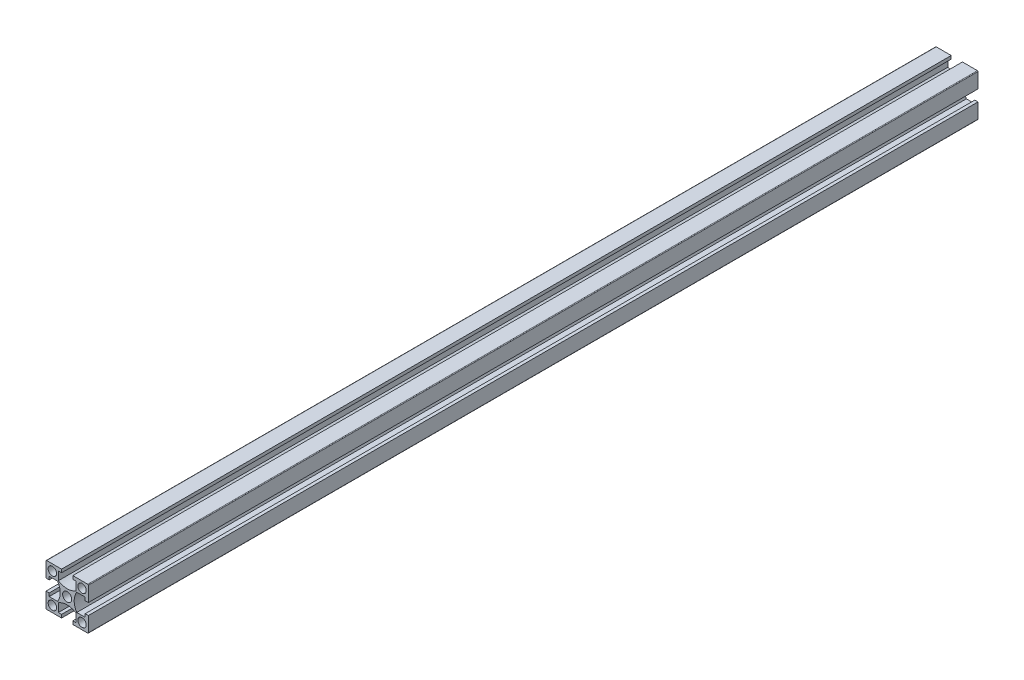
SolidWorks part; units mm, degrees
material "3.0255 (EN-AW 1350A)"
ref_plane "정면" through (0, 0, 0) normal (0, 0, 1) x (1, 0, 0)
ref_plane "윗면" through (0, 0, 0) normal (0, 1, 0) x (1, 0, 0)
ref_plane "우측면" through (0, 0, 0) normal (1, 0, 0) x (0, 0, -1)
sketch "스케치1" plane through (0, 0, 0) normal (0, 0, 1) x (1, 0, 0)
  line L0 (0, 32.0265) -> (0, -31.6588) construction
  line L1 (-10, 10) -> (-10, -10)
  line L2 (-10, 10) -> (10, 10)
  line L3 (-10, 2.65) -> (-8.5, 2.65)
  line L4 (13.6618, 0) -> (-11.6993, 0) construction
  line L5 (-8.5, 2.65) -> (-8.5, 4.15)
  line L6 (-8.5, 4.15) -> (-4.5032, 4.15)
  line L7 (-10, -2.65) -> (-8.5, -2.65)
  line L8 (-8.5, -2.65) -> (-8.5, -4.15)
  line L9 (-8.5, -4.15) -> (-4.5032, -4.15)
  line L10 (-10, -10) -> (10, -10)
  line L11 (10, 10) -> (10, -10)
  circle A0 centre (-7, 7) radius 2
  circle A1 centre (-7, -7) radius 2
  arc A2 (-4.5032, 4.15) -> (-4.5032, -4.15) centre (-11.0587, 0) cw
  circle A3 centre (0, 0) radius 2.15
  circle A4 centre (7, 7) radius 2
  circle A5 centre (7, -7) radius 2
  point P21 (-10, 0)
  point P23 (-3.3, 0)
  point P31 (0, -10)
  point P32 (0, 10)
  dimension "D3" = 4
  dimension "D9" = 6.7
  dimension "D10" = 4.3
  dimension "D11" = 7.7587
  dimension "D1" = 20
  dimension "D2" = 20
  dimension "D4" = 14
  dimension "D5" = 14
  dimension "D6" = 5.3
  dimension "D7" = 8.3
  dimension "D8" = 1.5
extrude "보스-돌출1" add sketch "스케치1" along normal blind 420 contours A0 | A4 | A3 | A5 | A1 | A2 L6 L5 L3 L1 L7 L8 L9 | L2 L11 L10 L1 region at (-6.6069, 0, 0) region at (-7, 7, 0) region at (-7, -7, 0) region at (0, 0, 0) region at (7, 7, 0) region at (7, -7, 0)
extrude "컷-돌출1" cut sketch "스케치1<3>" along normal up to next contours A2 L6 L5 L3 L1 L7 L8 L9 region at (-6.6069, 0, 0)
sketch "스케치1<3>" plane through (0, 0, 0) normal (0, 0, 1) x (1, 0, 0) same geometry as "스케치1"
pattern_circular "원형 패턴1" count 4 over 360 about axis through (0, 0, 420) along (0, 0, -1) of "컷-돌출1" reverse direction yes
fillet "필렛1" radius 0.3 4 edges at (10, -10, 210) (-10, -10, 210) (-10, 10, 210) (10, 10, 210)
sketch "스케치4" plane through (0, 10, 0) normal (0, 1, 0) x (1, 0, 0)
  line L0 (-4.15, -420) -> (4.15, -420) construction
  line L1 (4.15, 0) -> (-4.15, 0) construction
  circle A0 centre (0, -11) radius 2.5
  circle A1 centre (0, -409) radius 2.5
  dimension "D1" = 11
  dimension "D2" = 11
extrude "컷-돌출2" cut sketch "스케치4" against normal through all
sketch "스케치5" plane through (-10, 0, 0) normal (-1, 0, 0) x (0, 0, 1)
  line L0 (0, -2.65) -> (0, -9.7) construction
  line L1 (420, -4.15) -> (420, 4.15) construction
  circle A0 centre (131, 0) radius 2.5
  circle A1 centre (289, 0) radius 2.5
  dimension "D1" = 131
  dimension "D2" = 131
extrude "컷-돌출3" cut sketch "스케치5" against normal through all
sketch "스케치6" plane through (0, 10, 0) normal (0, 1, 0) x (1, 0, 0)
  line L0 (4.15, 0) -> (-4.15, 0) construction
  line L1 (-4.15, -420) -> (4.15, -420) construction
  circle A0 centre (0, -110) radius 2.5
  circle A1 centre (0, -310) radius 2.5
  dimension "D1" = 110
  dimension "D2" = 110
extrude "컷-돌출4" cut sketch "스케치6" against normal through all
